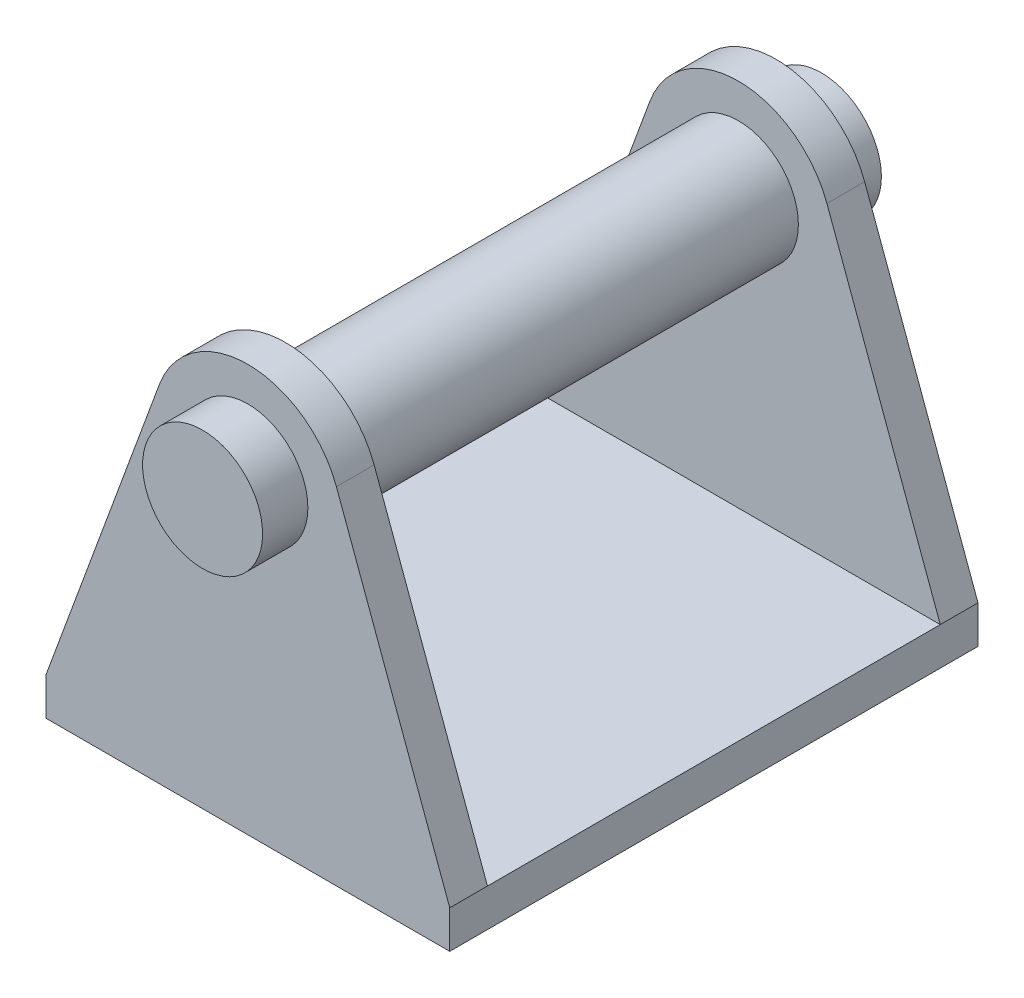
SolidWorks part; units mm, degrees
ref_plane "前视基准面" through (0, 0, 0) normal (0, 0, 1) x (1, 0, 0)
ref_plane "上视基准面" through (0, 0, 0) normal (0, 1, 0) x (1, 0, 0)
ref_plane "右视基准面" through (0, 0, 0) normal (1, 0, 0) x (0, 0, -1)
other "Configuration Table"
sketch "草图1" plane through (0, 0, 0) normal (0, 0, 1) x (1, 0, 0)
  line L0 (0, 0) -> (-76.2618, 0) construction
  line L1 (-53.5, 0) -> (-53.5, -10)
  line L2 (-53.5, -10) -> (53.5, -10)
  line L3 (0, -37.0783) -> (0, 122.6545) construction
  line L4 (53.5, 0) -> (53.5, -10)
  line L5 (-53.5, 0) -> (-23.4621, 81.6332)
  line L6 (53.5, 0) -> (23.4621, 81.6332)
  circle A0 centre (0, 73) radius 15.9
  arc A1 (23.4621, 81.6332) -> (-23.4621, 81.6332) centre (0, 73) ccw
  point P13 (0, -10)
  dimension "D1" = 31.8
  dimension "D2" = 50
  dimension "D3" = 73
  dimension "D4" = 10
  dimension "D5" = 107
extrude "凸台-拉伸1" add sketch "草图1" along normal blind 12 and the other way blind 152 contours A0
extrude "凸台-拉伸2" add sketch "草图1<3>" against normal blind 10
sketch "草图1<3>" plane through (0, 0, 0) normal (0, 0, 1) x (1, 0, 0) same geometry as "草图1"
ref_plane "基准面1" through (0, 0, -140) normal (0, 0, 1) x (1, 0, 0)
sketch "草图2" plane through (0, 0, -140) normal (0, 0, 1) x (1, 0, 0)
  line L0 (-53.5, 0) -> (-23.4621, 81.6332) construction
  line L1 (23.4621, 81.6332) -> (53.5, 0) construction
  line L2 (53.5, 0) -> (53.5, -10) construction
  line L3 (53.5, -10) -> (-53.5, -10) construction
  line L4 (-53.5, -10) -> (-53.5, 0) construction
  line L5 (-53.5, 0) -> (-23.4621, 81.6332)
  line L6 (23.4621, 81.6332) -> (53.5, 0)
  line L7 (53.5, 0) -> (53.5, -10)
  line L8 (53.5, -10) -> (-53.5, -10)
  line L9 (-53.5, -10) -> (-53.5, 0)
  arc A0 (23.4621, 81.6332) -> (-23.4621, 81.6332) centre (0, 73) ccw construction
  circle A1 centre (0, 73) radius 15.9 construction
  arc A2 (23.4621, 81.6332) -> (-23.4621, 81.6332) centre (0, 73) ccw
  circle A3 centre (0, 73) radius 15.9
extrude "凸台-拉伸3" add sketch "草图2" along normal blind 10
sketch "草图3" plane through (0, -10, 0) normal (0, -1, 0) x (1, 0, 0)
  line L16 (-53.5, -10) -> (-53.5, -130)
  line L17 (53.5, -10) -> (53.5, -130)
  line L18 (-53.5, -10) -> (53.5, -10)
  line L19 (-53.5, -130) -> (53.5, -130)
extrude "凸台-拉伸4" add sketch "草图3" against normal blind 10
